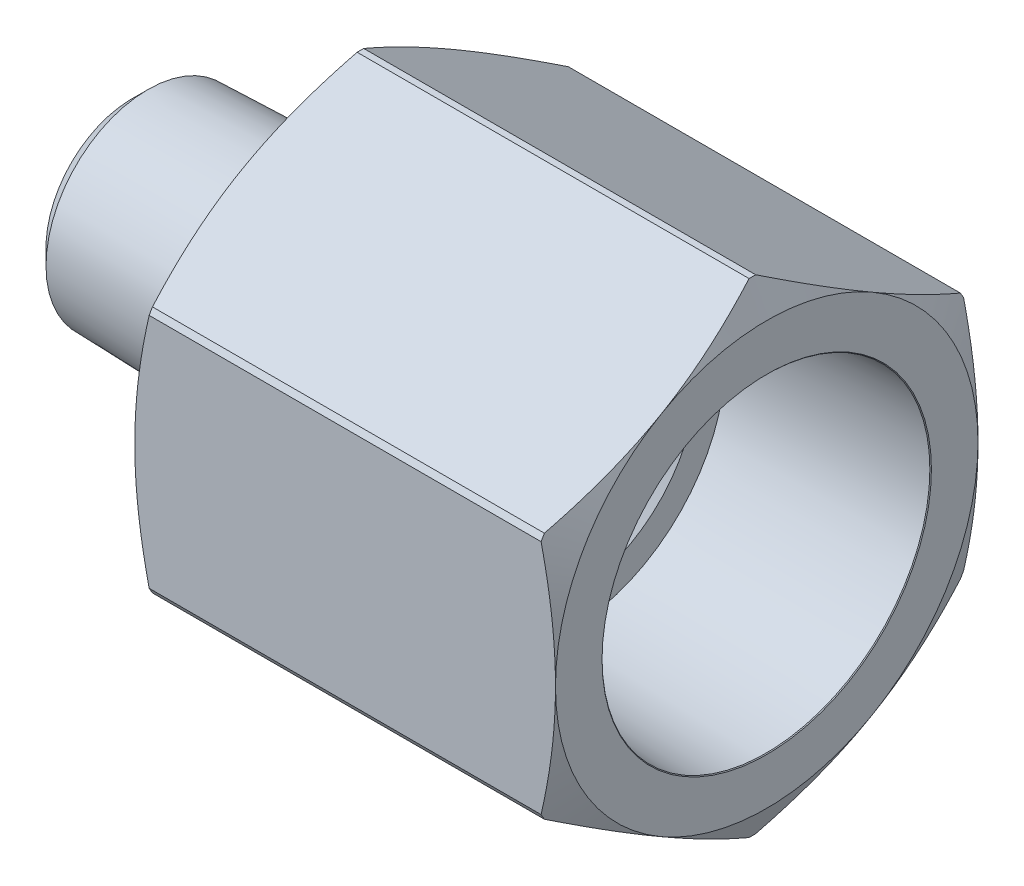
SolidWorks part; units mm, degrees
ref_plane "Front" through (0, 0, 0) normal (0, 0, 1) x (1, 0, 0)
ref_plane "Top" through (0, 0, 0) normal (0, 1, 0) x (1, 0, 0)
ref_plane "Right" through (0, 0, 0) normal (1, 0, 0) x (0, 0, -1)
sketch "Sketch1" plane through (0, 0, 0) normal (0, 0, 1) x (1, 0, 0)
  line L0 (-21.463, 0) -> (21.463, 0) construction
ref_plane "Plane1" through (-21.463, 0, 0) normal (1, 0, 0) x (0, 0, -1)
sketch "Sketch2" plane through (-21.463, 0, 0) normal (1, 0, 0) x (0, 0, -1)
  circle A0 centre (0, 0) radius 6.858
  dimension "OD" = 13.716
extrude "Extrude1" add sketch "Sketch2" along normal up to vertex (42.926 mm away) draft 1.783 up to point (21.463, 0, 0) draft outward yes
sketch "Sketch3" plane through (-21.463, 0, 0) normal (-1, 0, 0) x (0, 0, 1)
  circle A1 centre (0, 0) radius 6.858
  circle A2 centre (0, 0) radius 6.858
  dimension "D1" = 0
curve "Helix/Spiral1" parameters "pitch"=1.4111
sketch "Sketch4" plane through (0, 0, 0) normal (0, 0, 1) x (1, 0, 0)
  line L0 (-22.6977, 6.858) -> (-22.1686, 5.9415)
  line L1 (-22.1686, 5.9415) -> (-21.9922, 5.9415)
  line L2 (-21.9922, 5.9415) -> (-21.463, 6.858)
  line L3 (-22.6977, 6.858) -> (-21.463, 6.858) construction
  line L4 (-22.4331, 6.3997) -> (-21.7276, 6.3997) construction
  line L5 (-22.0804, 5.9415) -> (-22.0804, 6.858) construction
  line L6 (-22.6977, 6.858) -> (-21.3231, 7.1004)
  line L7 (-21.463, 6.858) -> (-21.3231, 7.1004)
  line L8 (-21.463, 6.858) -> (-21.463, -6.858) construction
  dimension "D1" = 10
  dimension "D2" = 0.1764
  dimension "D3" = 0.7056
  dimension "D4" = 60
sweep "Cut-Sweep1" [suppressed] cut profiles "Sketch4" path "Helix/Spiral1"
sketch "Sketch5" plane through (-21.463, 0, 0) normal (1, 0, 0) x (0, 0, -1)
  circle A0 centre (0, 0) radius 5.9415 construction
  circle A1 centre (0, 0) radius 5.8145
  dimension "D1" = 0.127
extrude "Cut-Extrude1" cut sketch "Sketch5" along normal through all draft 45 flip side to cut
ref_plane "Plane2" through (21.463, 0, 0) normal (1, 0, 0) x (0, 0, -1)
ref_plane "Plane3" through (-6.985, 0, 0) normal (-1, 0, 0) x (0, 0, 1)
sketch "Sketch8" plane through (-6.985, 0, 0) normal (-1, 0, 0) x (0, 0, 1)
  circle A2 centre (0, 0) radius 13.208
  circle A3 centre (0, 0) radius 13.208
  dimension "D1" = 6.35
extrude "Cut-Extrude4" cut sketch "Sketch8" against normal through all
sketch "Sketch9" plane through (-6.985, 0, 0) normal (1, 0, 0) x (0, 0, -1)
  circle A0 centre (0, 0) radius 6.858 construction
  circle A2 centre (0, 0) radius 5.9415
extrude "Cut-Extrude5" cut sketch "Sketch9" against normal blind 1.0583 flip side to cut
ref_plane "Plane4" through (-8.0433, 0, 0) normal (1, 0, 0) x (0, 0, -1)
sketch "Sketch10" plane through (-8.0433, 0, 0) normal (1, 0, 0) x (0, 0, -1)
  circle A1 centre (0, 0) radius 5.9415
  circle A2 centre (0, 0) radius 5.9415
  dimension "D1" = 0
extrude "Cut-Extrude6" cut sketch "Sketch10" against normal through all draft 45 flip side to cut
sketch "Sketch6" plane through (21.463, 0, 0) normal (1, 0, 0) x (0, 0, -1)
  line L1 (0, 16.4978) -> (-14.2875, 8.2489)
  line L2 (-14.2875, 8.2489) -> (-14.2875, -8.2489)
  line L3 (-14.2875, -8.2489) -> (0, -16.4978)
  line L4 (0, -16.4978) -> (14.2875, -8.2489)
  line L5 (14.2875, -8.2489) -> (14.2875, 8.2489)
  line L6 (14.2875, 8.2489) -> (0, 16.4978)
  circle A0 centre (0, 0) radius 14.2875 construction
  dimension "Hex" = 28.575
extrude "Extrude2" add sketch "Sketch6" against normal up to surface (28.448 mm away) up to face at (-6.985, 0, -5.9415)
sketch "Sketch18" plane through (-3.175, 0, 0) normal (0, 0, -1) x (-1, 0, 0)
  line L0 (-24.638, 14.2875) -> (-23.6665, 16.3708)
  line L1 (-24.638, 8.2489) -> (-24.638, 16.4978) construction
  line L2 (-23.6665, 16.3708) -> (2.8385, 16.3708)
  line L3 (2.8385, 16.3708) -> (3.81, 14.2875)
  line L4 (3.81, 8.2489) -> (3.81, 16.4978) construction
  line L5 (3.81, 14.2875) -> (3.81, 16.4978)
  line L6 (3.81, 16.4978) -> (-24.638, 16.4978)
  line L7 (-24.638, 16.4978) -> (-24.638, 14.2875)
  line L8 (3.81, 0) -> (-24.638, 0) construction
  line L9 (3.81, -8.2489) -> (3.81, 8.2489) construction
  line L10 (-24.638, -8.2489) -> (-24.638, 8.2489) construction
  line L13 (-10.414, 16.3708) -> (-10.414, 16.4978) construction
  dimension "D1" = 0.127
  dimension "D2" = 25
revolve "Cut-Revolve2" cut sketch "Sketch18" angle 360 about L8
sketch "Sketch7" plane through (21.463, 0, 0) normal (1, 0, 0) x (0, 0, -1)
  line L0 (0, 16.4978) -> (-14.2875, 8.2489) construction
  circle A0 centre (0, 0) radius 14.2875
ref_plane "Plane5" through (8.001, 0, 0) normal (1, 0, 0) x (0, 0, -1)
sketch "Sketch11" plane through (8.001, 0, 0) normal (1, 0, 0) x (0, 0, -1)
  circle A0 centre (0, 0) radius 10.668
  dimension "OD2" = 21.336
extrude "Cut-Extrude7" cut sketch "Sketch11" along normal through all draft 1.783 draft outward yes
sketch "Sketch12" plane through (8.001, 0, 0) normal (1, 0, 0) x (0, 0, -1)
  circle A0 centre (0, 0) radius 10.668 construction
  circle A1 centre (0, 0) radius 10.668
curve "Helix/Spiral2" parameters "pitch 2"=1.8143
sketch "Sketch16" plane through (21.463, 0, 0) normal (1, 0, 0) x (0, 0, -1)
  circle A2 centre (0, 0) radius 11.1379
  circle A3 centre (0, 0) radius 11.1379
  dimension "D1" = 0.0508
sketch "Sketch14" plane through (0, 0, 0) normal (0, 0, 1) x (1, 0, 0)
  line L0 (6.4135, 10.668) -> (8.001, 10.668) construction
  line L1 (8.001, 10.668) -> (7.3206, 9.4896) construction
  line L2 (7.3206, 9.4896) -> (7.0939, 9.4896)
  line L3 (7.0939, 9.4896) -> (6.4135, 10.668)
  line L4 (6.7537, 10.0788) -> (7.6608, 10.0788) construction
  line L5 (7.2072, 9.4896) -> (7.2072, 10.668) construction
  line L6 (6.4135, 10.668) -> (8.1809, 10.9796)
  line L7 (8.1809, 10.9796) -> (7.3206, 9.4896)
  line L8 (8.001, -10.668) -> (8.001, 10.668) construction
  dimension "D1" = 10
  dimension "D2" = 60
  dimension "D3" = 0.2268
  dimension "D4" = 0.9071
sweep "Sweep1" [suppressed] add profiles "Sketch14" path "Helix/Spiral2"
sketch "Sketch15" plane through (21.463, 0, 0) normal (1, 0, 0) x (0, 0, -1)
  line L6 (0, 16.4978) -> (-14.2875, 8.2489)
  line L7 (-14.2875, 8.2489) -> (-14.2875, -8.2489)
  line L8 (-14.2875, -8.2489) -> (0, -16.4978)
  line L9 (0, -16.4978) -> (14.2875, -8.2489)
  line L10 (14.2875, -8.2489) -> (14.2875, 8.2489)
  line L11 (14.2875, 8.2489) -> (0, 16.4978)
  line L12 (0, 16.4978) -> (-14.2875, 8.2489)
  line L13 (-14.2875, 8.2489) -> (-14.2875, -8.2489)
  line L14 (-14.2875, -8.2489) -> (0, -16.4978)
  line L15 (0, -16.4978) -> (14.2875, -8.2489)
  line L16 (14.2875, -8.2489) -> (14.2875, 8.2489)
  line L17 (14.2875, 8.2489) -> (0, 16.4978)
  dimension "D1" = 0
extrude "Cut-Extrude8" [suppressed] cut sketch "Sketch15" along normal through all
extrude "Cut-Extrude9" cut sketch "Sketch16" against normal blind 6.35 draft 45
sketch "Sketch17" plane through (0, 0, 0) normal (0, 0, 1) x (1, 0, 0)
  line L0 (8.001, 6.9342) -> (2.0062, 6.9342)
  line L1 (2.0062, 6.9342) -> (-2.0062, 3.556)
  line L2 (8.001, 6.9342) -> (8.001, 0)
  line L3 (8.001, 0) -> (-21.463, 0)
  line L4 (-21.463, 0) -> (-21.463, 3.556)
  line L5 (-21.463, -6.858) -> (-21.463, 6.858) construction
  line L6 (8.001, -10.668) -> (8.001, 10.668) construction
  line L7 (-2.0062, 3.556) -> (-21.463, 3.556)
  line L8 (0, 0) -> (0, 5.2451) construction
  line L9 (18.1183, 0) -> (15.9597, 0) construction
  dimension "ID2" = 13.8684
  dimension "ID1" = 7.112
revolve "Cut-Revolve1" cut sketch "Sketch17" angle 360 about L0
chamfer "Chamfer1" distance 1.8143 angle 45 1 edges at (8.001, 0, 6.9342)
equation "\"D3@Helix/Spiral1\" = \"L@Sketch1\""
equation "\"D2@Sketch4\" = \"pitch@Helix/Spiral1\"*.125"
equation "\"D3@Sketch4\" = \"pitch@Helix/Spiral1\"*.5"
equation "\"D1@Cut-Extrude5\" = \"pitch@Helix/Spiral1\"*.75"
equation "\"D1@Plane4\" = \"D1@Cut-Extrude5\""
equation "\"D3@Helix/Spiral2\" = \"thread engagement @Plane5\"+.250"
equation "\"D3@Sketch14\" = \"pitch 2@Helix/Spiral2\"*.125"
equation "\"D4@Sketch14\" = \"pitch 2@Helix/Spiral2\"*.50"
equation "\"D1@Chamfer1\"=\"pitch 2@Helix/Spiral2\""
